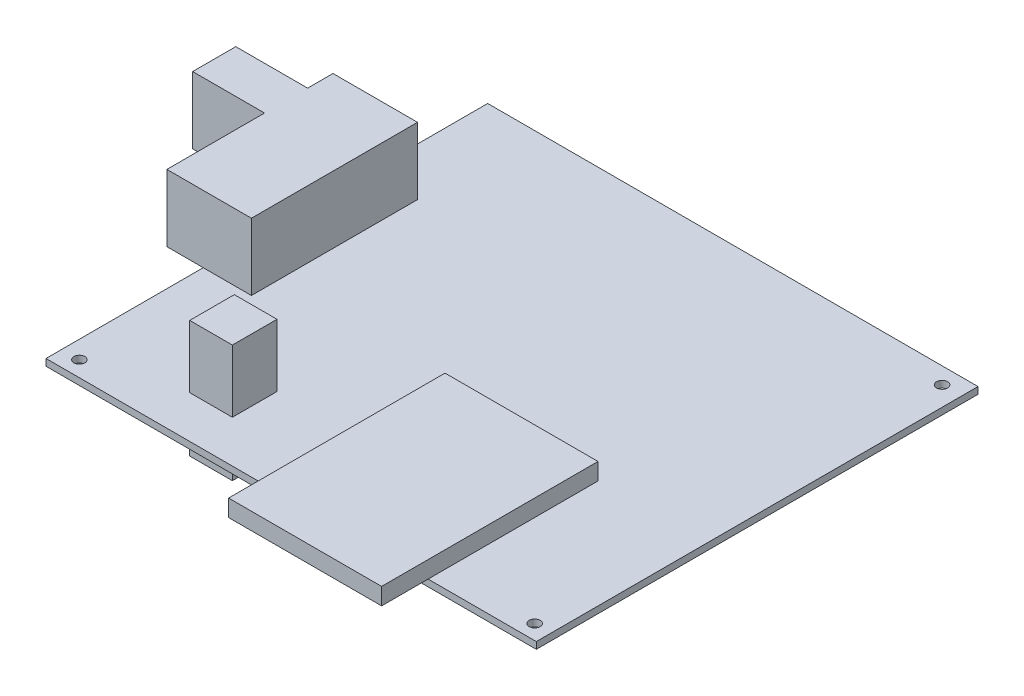
SolidWorks part; units mm, degrees
ref_plane "Front Plane" through (0, 0, 0) normal (0, 0, 1) x (1, 0, 0)
ref_plane "Top Plane" through (0, 0, 0) normal (0, 1, 0) x (1, 0, 0)
ref_plane "Right Plane" through (0, 0, 0) normal (1, 0, 0) x (0, 0, -1)
sketch "Sketch1" plane through (0, 0, 0) normal (0, 1, 0) x (1, 0, 0)
  line L0 (1.45, 1.85) -> (0, 1.85) construction
  line L1 (0, 0) -> (58, 0)
  line L2 (0, 0) -> (0, 52.25)
  line L3 (0, 52.25) -> (58, 52.25)
  line L4 (58, 0) -> (58, 52.25)
  line L5 (2.1, 1.2) -> (2.1, 0) construction
  line L6 (56.05, 1.1) -> (56.05, 0) construction
  line L7 (56.7, 1.75) -> (58, 1.75) construction
  line L8 (56.35, 50.3) -> (58, 50.3) construction
  line L9 (55.7, 50.95) -> (55.7, 52.25) construction
  line L10 (58, 26.125) -> (0, 26.125) construction
  line L11 (27.1, -5.5) -> (45.2, -5.5)
  line L12 (27.1, -5.5) -> (27.1, 20.1)
  line L13 (27.1, 20.1) -> (45.2, 20.1)
  line L14 (45.2, -5.5) -> (45.2, 20.1)
  line L15 (-4.3, 38.25) -> (5.7, 38.25)
  line L16 (-4.3, 38.25) -> (-4.3, 18.6)
  line L17 (-4.3, 18.6) -> (5.7, 18.6)
  line L18 (5.7, 38.25) -> (5.7, 18.6)
  line L19 (-4.3, 35.25) -> (-12.8, 35.25)
  line L20 (-4.3, 35.25) -> (-4.3, 30.15)
  line L21 (-4.3, 30.15) -> (-12.8, 30.15)
  line L22 (-12.8, 35.25) -> (-12.8, 30.15)
  line L23 (12, 10.276) -> (17.048, 10.276)
  line L24 (12, 10.276) -> (12, 5)
  line L25 (12, 5) -> (17.048, 5)
  line L26 (17.048, 10.276) -> (17.048, 5)
  line L27 (29, 52.25) -> (29, 0) construction
  circle A0 centre (2.1, 1.85) radius 0.65
  circle A1 centre (56.05, 1.75) radius 0.65
  circle A2 centre (55.7, 50.3) radius 0.65
  dimension "D1" = 1.3
  dimension "D2" = 1.45
  dimension "D3" = 1.2
  dimension "D4" = 1.1
  dimension "D5" = 1.3
  dimension "D6" = 1.65
  dimension "D7" = 1.3
  dimension "D8" = 58
  dimension "D9" = 52.25
  dimension "D10" = 19.65
  dimension "D11" = 12.8
  dimension "D12" = 25.6
  dimension "D13" = 18.1
  dimension "D14" = 5.5
  dimension "D15" = 8.5
  dimension "D16" = 5.7
  dimension "D17" = 5.1
  dimension "D18" = 18.5
  dimension "D19" = 3
  dimension "D20" = 14
  dimension "D21" = 5
  dimension "D22" = 12
extrude "Boss-Extrude1" add sketch "Sketch1" against normal blind 0.8 contours L15 L18 L17 L2 L1 L12 L13 L14 L4 L3 A2 A1 A0 | L1 L14 L13 L12 | L18 L15 L2 L17 | L26 L23 L24 L25 region at (29.2685, 0, -28.5479) region at (36.15, 0, -10.05) region at (2.85, 0, -28.425) region at (14.524, 0, -7.638)
extrude "Boss-Extrude2" add sketch "Sketch1<3>" along normal blind 7.92 contours L18 L15 L2 L17 | L16 L17 L2 L15 | L19 L22 L21 L16 region at (-2.15, 0, -28.425) region at (2.85, 0, -28.425) region at (-8.55, 0, -32.7)
sketch "Sketch1<3>" plane through (0, 0, 0) normal (0, 1, 0) x (1, 0, 0) same geometry as "Sketch1"
extrude "Boss-Extrude3" add sketch "Sketch1<4>" along normal blind 2 contours L1 L14 L13 L12 | L11 L14 L1 L12 region at (36.15, 0, -10.05) region at (36.15, 0, 2.75)
sketch "Sketch1<4>" plane through (0, 0, 0) normal (0, 1, 0) x (1, 0, 0) same geometry as "Sketch1"
extrude "Boss-Extrude4" add sketch "Sketch1<5>" against normal blind 5.7 and the other way blind 8.2 from surface contours L26 L23 L24 L25 region at (14.524, 0, -7.638) starting at face at (55.7, -0.8, -49.65)
sketch "Sketch1<5>" plane through (0, 0, 0) normal (0, 1, 0) x (1, 0, 0) same geometry as "Sketch1"
ref_point "Point1"
ref_axis "Axis1" through (29, 0, -26.125) along (0, 1, 0)
equation "\"D1@Boss-Extrude2\"=10.46-2.54"
equation "\"D1@Boss-Extrude4\"=6.5-.8"
equation "\"D2@Boss-Extrude4\"=15.5-6.5-.8"
